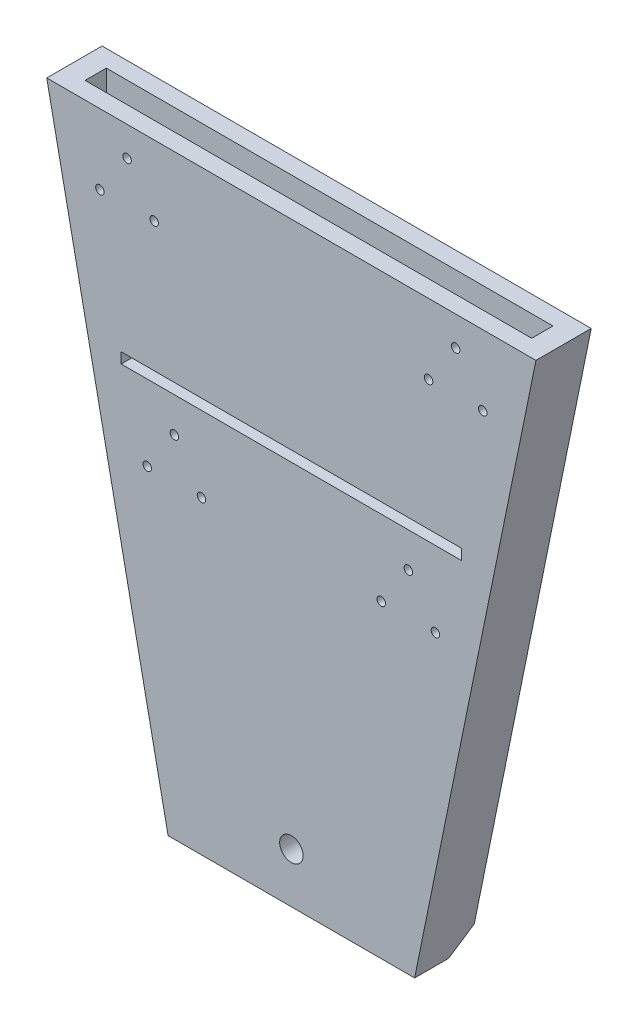
SolidWorks part; units mm, degrees
ref_plane "前视基准面" through (0, 0, 0) normal (0, 0, 1) x (1, 0, 0)
ref_plane "上视基准面" through (0, 0, 0) normal (0, 1, 0) x (1, 0, 0)
ref_plane "右视基准面" through (0, 0, 0) normal (1, 0, 0) x (0, 0, -1)
other "Configuration Table"
sketch "草图1" plane through (0, 0, 0) normal (0, 0, 1) x (1, 0, 0)
  line L0 (-60, 0) -> (60, 0)
  line L1 (0, 77.3448) -> (0, -71.5734) construction
  line L2 (-115, 270) -> (115, 270)
  line L3 (-115, 270) -> (-60, 0)
  line L4 (115, 270) -> (60, 0)
  point P3 (0, 0)
  point P8 (0, 270)
  dimension "D1" = 120
  dimension "D2" = 230
  dimension "D3" = 270
extrude "凸台-拉伸1" add sketch "草图1" along normal blind 8
sketch "草图2" plane through (0, 0, 8) normal (0, 0, 1) x (1, 0, 0)
  line L0 (-60, 0) -> (60, 0) construction
  line L1 (0, -1000) -> (0, 0.3) construction
  line L2 (0, 26.71) -> (0, 57.7278) construction
  line L3 (0.005, 0.31) -> (0, 0.3)
  line L4 (0, 26.71) -> (12.1089, 26.71)
  line L6 (0, 0.3) -> (17.4887, 0.3)
  line L7 (12.1089, 26.71) -> (17.4887, 0.3)
  line L8 (-115, 270) -> (-60, 0) construction
  arc A0 (0, 26.71) -> (0.005, 0.31) centre (0, 13.51) ccw
  dimension "D1" = 26.4
  dimension "D2" = 13.51
  dimension "D3" = 14.5
  dimension "D5" = 13.21
extrude "切除-拉伸1" cut sketch "草图2" against normal blind 8.5
sketch "草图3" plane through (0, 0, 8) normal (0, 0, 1) x (1, 0, 0)
  line L0 (-94.3261, 168.51) -> (94.3261, 168.51)
  line L1 (-115, 270) -> (-60, 0) construction
  line L2 (60, 0) -> (115, 270) construction
  line L4 (-96.3631, 178.51) -> (96.3631, 178.51)
  line L5 (-107.8704, 235) -> (107.8704, 235)
  point P0 (-115, 270)
  point P14 (0, 178.51)
  point P15 (0, 13.51)
  dimension "D1" = 155
  dimension "D2" = 10
  dimension "D3" = 35
sketch "草图5" plane through (0, 0, 0) normal (0, 0, -1) x (-1, 0, 0)
  line L4 (60, 0) -> (115, 270)
  line L5 (115, 270) -> (-115, 270)
  line L6 (-115, 270) -> (-60, 0)
  line L7 (-60, 0) -> (60, 0)
  line L8 (60, 0) -> (115, 270)
  line L9 (115, 270) -> (-115, 270)
  line L10 (-115, 270) -> (-60, 0)
  line L11 (-60, 0) -> (60, 0)
  dimension "D1" = 0
extrude "凸台-拉伸2" add sketch "草图5" along normal blind 8
sketch "草图6" plane through (0, 0, 8) normal (0, 0, 1) x (1, 0, 0)
  line L4 (-115, 270) -> (-60, 0)
  line L5 (-60, 0) -> (60, 0)
  line L6 (60, 0) -> (115, 270)
  line L7 (115, 270) -> (-115, 270)
  line L8 (-115, 270) -> (-60, 0)
  line L9 (-60, 0) -> (60, 0)
  line L10 (60, 0) -> (115, 270)
  line L11 (115, 270) -> (-115, 270)
  point P2 (0, 13.51)
  dimension "D1" = 0
extrude "凸台-拉伸3" add sketch "草图6" along normal blind 10
sketch "草图7" plane through (0, 0, 18) normal (0, 0, 1) x (1, 0, 0)
  circle A0 centre (0, 13.51) radius 5.5
  dimension "D1" = 11
extrude "切除-拉伸2" cut sketch "草图7" against normal blind 22
ref_plane "基准面1" through (0, 0, 18) normal (0, 0, 1) x (1, 0, 0)
sketch "草图9" plane through (0, 0, 18) normal (0, 0, 1) x (1, 0, 0)
  line L0 (-60, 0) -> (60, 0)
  line L1 (60, 0) -> (57.963, -10)
  line L2 (57.963, -10) -> (-57.963, -10)
  line L3 (-57.963, -10) -> (-60, 0)
  line L4 (60, 0) -> (115, 270) construction
  line L5 (-115, 270) -> (-60, 0) construction
  line L6 (60, 0) -> (115, 270)
  line L7 (-115, 270) -> (-60, 0)
  dimension "D1" = 10
extrude "凸台-拉伸5" add sketch "草图9" against normal blind 26 contours L3 L2 L1 L0 region at (0, -4.9712, 18)
ref_plane "基准面2" through (0, 0, -8) normal (0, 0, 1) x (1, 0, 0)
sketch "草图11" plane through (0, 0, -8) normal (0, 0, 1) x (1, 0, 0)
  line L0 (110.9179, 270) -> (53.8808, -10)
  line L1 (-110.9179, 270) -> (-53.8808, -10)
  line L2 (109.6932, 270) -> (52.6562, -10)
  line L3 (-109.6932, 270) -> (-52.6562, -10)
  line L4 (115, 270) -> (-115, 270)
  line L5 (-115, 270) -> (-57.963, -10)
  line L6 (-57.963, -10) -> (57.963, -10)
  line L7 (57.963, -10) -> (115, 270)
  line L8 (115, 270) -> (-115, 270)
  line L9 (-115, 270) -> (-57.963, -10)
  line L10 (-57.963, -10) -> (57.963, -10)
  line L11 (57.963, -10) -> (115, 270)
  dimension "D2" = 4
  dimension "D3" = 4
  dimension "D4" = 1.2
  dimension "D5" = 1.2
  dimension "D1" = 0
sketch "草图12" plane through (0, 0, -8) normal (0, 0, 1) x (1, 0, 0)
  line L0 (-115, 270) -> (-60, 0) construction
  line L1 (60, 0) -> (115, 270) construction
  line L2 (-115, 270) -> (-60, 0)
  line L3 (60, 0) -> (115, 270)
  line L4 (60, 0) -> (-60, 0)
  line L5 (57.963, -10) -> (60, 0)
  line L6 (-57.963, -10) -> (57.963, -10)
  line L7 (-60, 0) -> (-57.963, -10)
  line L8 (60, 0) -> (-60, 0)
  line L9 (57.963, -10) -> (60, 0)
  line L10 (-57.963, -10) -> (57.963, -10)
  line L11 (-60, 0) -> (-57.963, -10)
  line L12 (-109.6932, 270) -> (-52.6562, -10) construction
  line L13 (109.6932, 270) -> (52.6562, -10) construction
  line L14 (-110.9179, 270) -> (-53.8808, -10) construction
  line L15 (110.9179, 270) -> (53.8808, -10) construction
  line L16 (115, 270) -> (-115, 270)
  line L17 (-115, 270) -> (-57.963, -10)
  line L18 (-57.963, -10) -> (57.963, -10)
  line L19 (57.963, -10) -> (115, 270)
  line L20 (115, 270) -> (-115, 270)
  line L21 (-115, 270) -> (-57.963, -10)
  line L22 (-57.963, -10) -> (57.963, -10)
  line L23 (57.963, -10) -> (115, 270)
  line L24 (-109.6932, 270) -> (-52.6562, -10)
  line L25 (109.6932, 270) -> (52.6562, -10)
  line L26 (-110.9179, 270) -> (-53.8808, -10)
  line L27 (110.9179, 270) -> (53.8808, -10)
  dimension "D1" = 0
  dimension "D2" = 0
extrude "切除-拉伸4" cut sketch "草图12" along normal blind 21 contours L25 L8 L24 L22 region at (0, -4.9684, -8)
chamfer "倒角6" distance 5 angle 45 1 edges at (0, 0, -8)
chamfer "倒角8" distance 10 angle 45 2 edges at (-55.3096, -10, -8) (55.3096, -10, -8)
sketch "草图13" plane through (0, 270, 0) normal (0, 1, 0) x (1, 0, 0)
  line L1 (-105, 0) -> (105, 0)
  line L2 (-105, 0) -> (-105, -10)
  line L3 (-105, -10) -> (105, -10)
  line L4 (105, 0) -> (105, -10)
  line L5 (-105, 0) -> (105, -10) construction
  line L6 (-105, -10) -> (105, 0) construction
  line L7 (115, -18) -> (-115, -18) construction
  line L9 (-115, -18) -> (-115, 8) construction
  point P4 (0, -5)
  dimension "D1" = 210
  dimension "D2" = 10
  dimension "D3" = 13
  dimension "D4" = 115
extrude "切除-拉伸5" cut sketch "草图13" against normal blind 15
sketch "草图14" plane through (0, 0, 18) normal (0, 0, 1) x (1, 0, 0)
  line L0 (-96.3631, 178.51) -> (96.3631, 178.51) construction
  line L1 (-96.3631, 178.51) -> (96.3631, 178.51)
  line L2 (-94.3261, 168.51) -> (94.3261, 168.51) construction
  line L3 (-107.8704, 235) -> (107.8704, 235) construction
  line L4 (115, 270) -> (-115, 270)
  line L5 (-115, 270) -> (-57.963, -10)
  line L6 (-57.963, -10) -> (57.963, -10)
  line L7 (57.963, -10) -> (115, 270)
  line L8 (115, 270) -> (-115, 270)
  line L9 (-115, 270) -> (-57.963, -10)
  line L10 (-57.963, -10) -> (57.963, -10)
  line L11 (57.963, -10) -> (115, 270)
  line L12 (-94.3261, 168.51) -> (94.3261, 168.51)
  line L13 (-107.8704, 235) -> (107.8704, 235)
  line L14 (0, 270) -> (0, -10) construction
  line L15 (-80, 176.01) -> (80, 176.01)
  line L16 (-80, 176.01) -> (-80, 171.01)
  line L17 (-80, 171.01) -> (80, 171.01)
  line L18 (80, 176.01) -> (80, 171.01)
  line L19 (-80, 176.01) -> (80, 171.01) construction
  line L20 (-80, 171.01) -> (80, 176.01) construction
  point P14 (0, 173.51)
  dimension "D2" = 160
  dimension "D3" = 5
  dimension "D4" = 5
  dimension "D1" = 0
extrude "切除-拉伸6" cut sketch "草图14" against normal blind 10 contours L18 L15 L16 L17 region at (0, 173.51, 18)
sketch "草图16" plane through (0, 0, 18) normal (0, 0, 1) x (1, 0, 0)
  line L0 (0, 270) -> (0, -27.9065) construction
  line L2 (115, 270) -> (-115, 270) construction
  line L3 (-107.8704, 235) -> (107.8704, 235) construction
  line L4 (-94.3261, 168.51) -> (94.3261, 168.51) construction
  line L5 (-96.3631, 178.51) -> (96.3631, 178.51) construction
  line L6 (115, 270) -> (-115, 270)
  line L7 (-107.8704, 235) -> (107.8704, 235)
  line L8 (-94.3261, 168.51) -> (94.3261, 168.51)
  line L9 (-96.3631, 178.51) -> (96.3631, 178.51)
  line L11 (-90.2182, 178.51) -> (90.2182, 178.51)
  line L12 (-90.2182, 178.51) -> (-90.2182, 168.51)
  line L13 (-90.2182, 168.51) -> (90.2182, 168.51)
  line L14 (90.2182, 178.51) -> (90.2182, 168.51)
  line L15 (-90.2182, 178.51) -> (90.2182, 168.51) construction
  line L16 (-90.2182, 168.51) -> (90.2182, 178.51) construction
  circle A0 centre (-77.25, 256.1426) radius 2
  circle A1 centre (-90, 237) radius 2
  circle A2 centre (-64.5, 237) radius 2
  circle A3 centre (64.5, 237) radius 2
  circle A4 centre (90, 237) radius 2
  circle A5 centre (77.25, 256.1426) radius 2
  circle A6 centre (-55, 154.6526) radius 2
  circle A7 centre (-67.75, 135.51) radius 2
  circle A8 centre (-42.25, 135.51) radius 2
  circle A9 centre (42.25, 135.51) radius 2
  circle A10 centre (67.75, 135.51) radius 2
  circle A11 centre (55, 154.6526) radius 2
  point P15 (0, 173.51)
  dimension "D6" = 4
  dimension "D7" = 4
  dimension "D8" = 4
  dimension "D15" = 4
  dimension "D16" = 4
  dimension "D17" = 4
  dimension "D1" = 33
  dimension "D2" = 33
  dimension "D3" = 25.5
  dimension "D4" = 23
  dimension "D5" = 23
  dimension "D9" = 90
  dimension "D10" = 23
  dimension "D11" = 23
  dimension "D12" = 25.5
  dimension "D13" = 33
  dimension "D14" = 33
  dimension "D18" = 55
extrude "切除-拉伸7" cut sketch "草图16" against normal blind 10 contours A0 | A1 | A2 | A5 | A3 | A4 | A6 | A8 | A11 | A9 | A10 | A7 region at (-64.5, 237, 18) region at (64.5, 237, 18) region at (90, 237, 18) region at (-90, 237, 18) region at (-77.25, 256.1426, 18) region at (77.25, 256.1426, 18) region at (-55, 154.6526, 18) region at (-42.25, 135.51, 18) region at (42.25, 135.51, 18) region at (67.75, 135.51, 18) region at (55, 154.6526, 18)
sketch "草图17" plane through (0, 0, 18) normal (0, 0, 1) x (1, 0, 0)
  point P0 (-60.2489, 215.8027)
  point P2 (-96.3631, 178.51)
sketch "草图18" plane through (0, 0, 0) normal (0, -1, 0) x (1, 0, 0)
  line L4 (-54.6932, 13) -> (-54.6932, -3)
  line L5 (-54.6932, -3) -> (54.6932, -3)
  line L6 (54.6932, -3) -> (54.6932, 13)
  line L7 (54.6932, 13) -> (-54.6932, 13)
  line L8 (-54.6932, 13) -> (-54.6932, -3)
  line L10 (54.6932, -3) -> (54.6932, 13)
  line L11 (54.6932, 13) -> (-54.6932, 13)
  line L13 (-54.6932, -3) -> (54.6932, -3)
  dimension "D1" = 0
extrude "凸台-拉伸7" add sketch "草图18" along normal blind 2
chamfer "倒角10" distance 2 angle 45 1 edges at (0, -2, -3)
